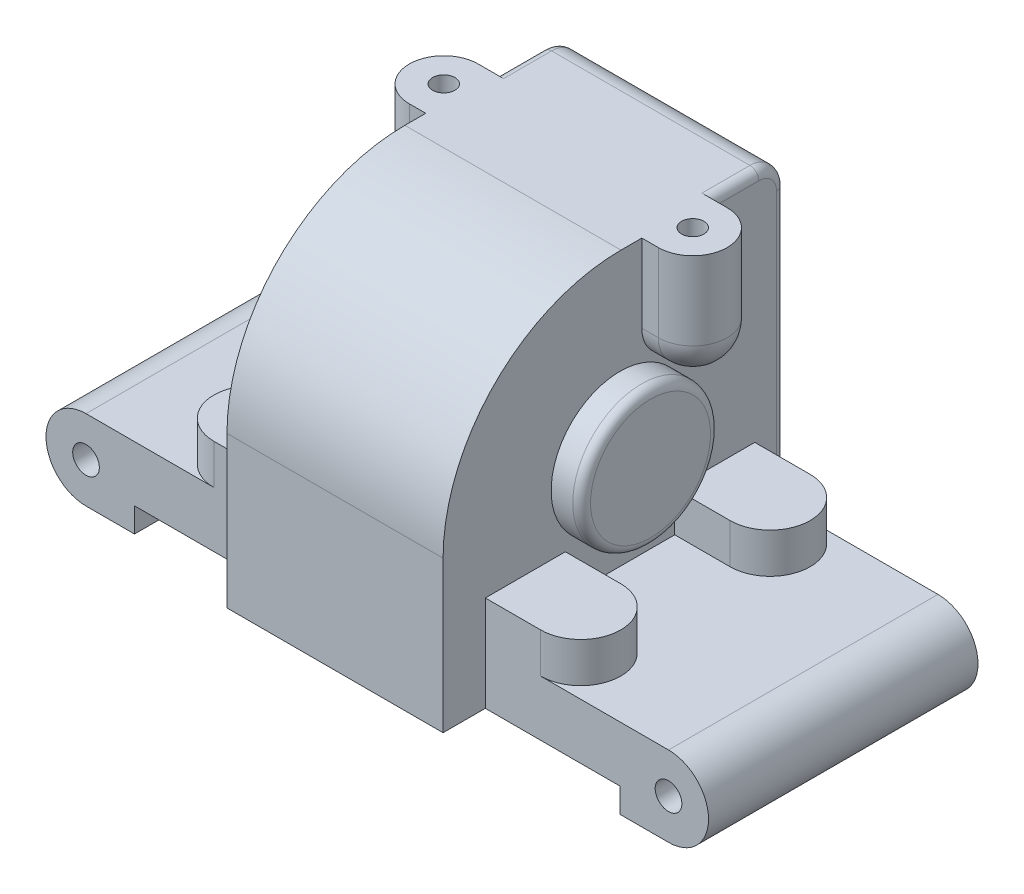
SolidWorks part; units mm, degrees
ref_plane "Front Plane" through (0, 0, 0) normal (0, 0, 1) x (1, 0, 0)
ref_plane "Top Plane" through (0, 0, 0) normal (0, 1, 0) x (1, 0, 0)
ref_plane "Right Plane" through (0, 0, 0) normal (1, 0, 0) x (0, 0, -1)
sketch "Sketch1" plane through (0, 0, 0) normal (0, 0, 1) x (1, 0, 0)
  line L0 (32.75, 0) -> (-32.75, 0) construction
  line L1 (32.75, -4.5) -> (-32.75, -4.5)
  line L2 (32.75, 4.5) -> (-32.75, 4.5)
  line L4 (-27.3, -4.5) -> (27.3, -4.5)
  line L5 (-27.3, -4.5) -> (-27.3, -1.75)
  line L6 (-27.3, -1.75) -> (27.3, -1.75)
  line L7 (27.3, -4.5) -> (27.3, -1.75)
  arc A0 (32.75, -4.5) -> (32.75, 4.5) centre (32.75, 0) ccw
  arc A1 (-32.75, 4.5) -> (-32.75, -4.5) centre (-32.75, 0) ccw
  circle A2 centre (32.75, 0) radius 1.5
  circle A3 centre (-32.75, 0) radius 1.5
  point P2 (0, 0)
  point P12 (0, -1.75)
  dimension "D5" = 3
  dimension "D1" = 65.5
  dimension "D2" = 9
  dimension "D3" = 54.6
  dimension "D4" = 2.75
extrude "Boss-Extrude1" add sketch "Sketch1" along normal blind 30.3 contours L2 A1 L1 L5 L6 L7 A0 region at (0, 0.9599, 0)
sketch "Sketch2" plane through (0, 0, 0) normal (1, 0, 0) x (0, 0, -1)
  line L0 (-35.05, -1.75) -> (3.45, -1.75)
  line L1 (3.45, -1.75) -> (3.45, 32.25)
  line L2 (0.45, 35.25) -> (-15.05, 35.25)
  line L3 (-35.05, 15.25) -> (-35.05, -1.75)
  line L5 (-30.3, -1.75) -> (0, -1.75) construction
  line L6 (0, -4.5) -> (0, 4.5) construction
  arc A0 (-15.05, 35.25) -> (-35.05, 15.25) centre (-15.05, 15.25) ccw
  arc A1 (3.45, 32.25) -> (0.45, 35.25) centre (0.45, 32.25) ccw
  point P10 (-18.3932, 15.25)
  point P13 (3.45, 35.25)
  dimension "D2" = 20
  dimension "D5" = 3
  dimension "D1" = 3.45
  dimension "D3" = 37
  dimension "D4" = 18.5
extrude "Boss-Extrude2" add sketch "Sketch2" along normal mid plane 24.3
sketch "Sketch3" plane through (0, 35.25, 0) normal (0, 1, 0) x (1, 0, 0)
  line L0 (14, -8.825) -> (-14, -8.825) construction
  line L1 (14, -12.7) -> (-14, -12.7)
  line L2 (14, -4.95) -> (-14, -4.95)
  line L3 (12.15, 3.45) -> (-12.15, 3.45) construction
  arc A0 (14, -12.7) -> (14, -4.95) centre (14, -8.825) ccw
  arc A1 (-14, -4.95) -> (-14, -12.7) centre (-14, -8.825) ccw
  point P2 (0, -8.825)
  point P7 (-17.875, -8.825)
  point P8 (17.875, -8.825)
  point P9 (0, 0)
  dimension "D1" = 28
  dimension "D2" = 7.75
  dimension "D3" = 8.4
extrude "Boss-Extrude3" add sketch "Sketch3" against normal blind 12.66
fillet "Fillet1" radius 3.875 6 edges at (-13.075, 22.59, 4.95) (-13.075, 22.59, 12.7) (13.075, 22.59, 12.7) (13.075, 22.59, 4.95) (-17.875, 22.59, 8.825) (17.875, 22.59, 8.825)
sketch "Sketch4" plane through (0, 4.5, 0) normal (0, 1, 0) x (1, 0, 0)
  line L0 (-18.375, -4.5) -> (18.375, -4.5) construction
  line L1 (-18.375, 0) -> (18.375, 0)
  line L2 (-18.375, -9) -> (18.375, -9)
  line L3 (32.75, 0) -> (12.15, 0) construction
  line L4 (22.875, -4.5) -> (-22.875, -4.5) construction
  line L5 (18.375, -25.8) -> (-18.375, -25.8) construction
  line L6 (18.375, -30.3) -> (-18.375, -30.3)
  line L7 (18.375, -21.3) -> (-18.375, -21.3)
  line L8 (-12.15, -30.3) -> (-32.75, -30.3) construction
  arc A0 (-18.375, 0) -> (-18.375, -9) centre (-18.375, -4.5) ccw
  arc A1 (18.375, -9) -> (18.375, 0) centre (18.375, -4.5) ccw
  arc A2 (18.375, -30.3) -> (18.375, -21.3) centre (18.375, -25.8) ccw
  arc A3 (-18.375, -21.3) -> (-18.375, -30.3) centre (-18.375, -25.8) ccw
  point P2 (0, -4.5)
  point P10 (-22.875, -4.5)
  point P11 (0, -25.8)
  point P13 (22.875, -4.5)
  point P23 (0, 0)
  point P24 (0, 0)
  dimension "D2" = 4.5
  dimension "D1" = 45.75
extrude "Boss-Extrude4" add sketch "Sketch4" along normal blind 4.5
sketch "Sketch5" plane through (0, 35.25, 0) normal (0, 1, 0) x (1, 0, 0)
  circle A0 centre (14, -8.825) radius 1.25
  circle A1 centre (-14, -8.825) radius 1.25
  dimension "D1" = 2.5
extrude "Cut-Extrude1" cut sketch "Sketch5" against normal blind 10
sketch "Sketch6" plane through (0, 0, 0) normal (1, 0, 0) x (0, 0, -1)
  line L1 (-9, 4.5) -> (-21.3, 4.5) construction
  line L2 (0, -1.75) -> (3.45, -1.75) construction
  circle A0 centre (-15.15, 15.75) radius 7.75
  point P2 (-7.4, 15.75)
  point P3 (0, 0)
  point P4 (-15.15, 4.5)
  point P7 (0, 0)
  dimension "D1" = 15.5
  dimension "D2" = 17.5
extrude "Boss-Extrude5" add sketch "Sketch6" along normal mid plane 31.16
fillet "Fillet2" radius 1 2 edges at (-15.58, 15.75, 7.4) (15.58, 15.75, 7.4)
fillet "Fillet3" radius 1 6 edges at (12.15, 35.25, 2.25) (12.15, 34.3713, -2.5713) (-12.15, 15.25, -3.45) (-12.15, 34.3713, -2.5713) (12.15, 15.25, -3.45) (-12.15, 35.25, 2.25)
sketch "Sketch7" plane through (0, -1.75, 0) normal (0, -1, 0) x (1, 0, 0)
  line L0 (-27.3, 0) -> (-12.15, 0) construction
  line L1 (0, -21.175) -> (0, 21.175) construction
  circle A0 centre (-19, 5.2) radius 2
  circle A1 centre (-19, 25.2) radius 2
  circle A2 centre (19, 5.2) radius 2
  circle A3 centre (19, 25.2) radius 2
  point P4 (0, 0)
  dimension "D4" = 4
  dimension "D1" = 20
  dimension "D2" = 19
  dimension "D3" = 5.2
extrude "Cut-Extrude2" cut sketch "Sketch7" against normal blind 8
